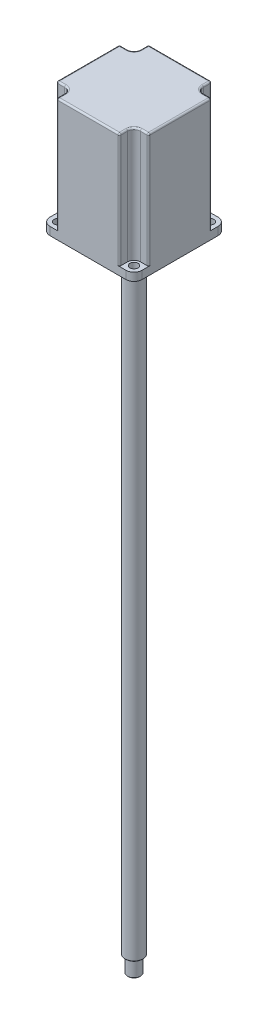
SolidWorks part; units mm, degrees
note: '?' marks a value the reader was unsure of.
material "1023 Carbon Steel Sheet (SS)"
ref_plane "Front" through (0, 0, 0) normal (0, 0, 1) x (1, 0, 0)
ref_plane "Top" through (0, 0, 0) normal (0, 1, 0) x (1, 0, 0)
ref_plane "Right" through (0, 0, 0) normal (1, 0, 0) x (0, 0, -1)
ref_axis "Axis1" through (-84.4107, 0, 0) along (1, 0, 0)?
ref_axis "Axis2" through (0, 64.3378, 0) along (0, -1, 0)?
ref_axis "Axis3" through (0, 0, -102.329) along (0, 0, 1)?
sketch "Sketch1" plane through (0, 0, 0) normal (0, 1, 0) x (1, 0, 0)
  line L1 (-28.5, -28.5) -> (28.5, -28.5)
  line L2 (-28.5, -28.5) -> (-28.5, 28.5)
  line L3 (-28.5, 28.5) -> (28.5, 28.5)
  line L4 (28.5, -28.5) -> (28.5, 28.5)
  line L5 (-28.5, -28.5) -> (28.5, 28.5) construction
  line L6 (-28.5, 28.5) -> (28.5, -28.5) construction
  point P0 (0, 0)
  dimension "D1" = 57
  dimension "D2" = 57
extrude "Extrude1" add sketch "Sketch1" along normal blind 76
hole_wizard "Ø5.0 (5) Diameter Hole1" positions "Sketch5" profile "Sketch4" hole size "Ø5.0" standard "ISO" end condition through all
sketch "Sketch5" plane through (0, 0, 0) normal (0, -1, 0) x (1, 0, 0)
  line L0 (-28.5, 28.5) -> (28.5, -28.5) construction
  line L3 (28.5, 28.5) -> (-28.5, -28.5) construction
  point P0 (-23.5, 23.5)
  point P1 (23.5, 23.5)
  point P3 (23.5, -23.5)
  point P5 (-23.5, -23.5)
  dimension "D1" = 47
  dimension "D2" = 47
sketch "Sketch4" plane through (-23.5, 0, 23.5) normal (1, 0, 0) x (0, 0, -1)
  line L0 (0, 0) -> (0, 76)
  line L1 (0, 76) -> (2.5, 76)
  line L2 (2.5, 76) -> (2.5, 0)
  line L5 (2.5, 0) -> (0, 0)
  line L11 (0, -6.35) -> (0, 107.95) construction
  dimension "Thru Hole Dia." = 5
  dimension "Thru Hole Depth" = 76
sketch "Sketch6" plane through (0, 76, 0) normal (0, 1, 0) x (1, 0, 0)
  line L0 (-19.5, 23.5) -> (-19.5, 32.5117)
  line L1 (-19.5, 32.5117) -> (-33.9089, 32.5117)
  line L2 (-33.9089, 32.5117) -> (-33.9089, 19.5)
  line L3 (-33.9089, 19.5) -> (-23.5, 19.5)
  line L4 (19.5, 23.5) -> (19.5, 36.4716)
  line L5 (19.5, 36.4716) -> (41.1684, 36.4716)
  line L6 (41.1684, 36.4716) -> (41.1684, 19.5)
  line L7 (41.1684, 19.5) -> (23.5, 19.5)
  line L8 (23.5, -19.5) -> (44.2522, -19.5)
  line L9 (44.2522, -19.5) -> (44.2522, -40.0504)
  line L10 (44.2522, -40.0504) -> (19.5, -40.0504)
  line L11 (19.5, -40.0504) -> (19.5, -23.5)
  line L12 (-23.5, -19.5) -> (-37.6708, -19.5)
  line L13 (-37.6708, -19.5) -> (-37.6708, -37.8282)
  line L14 (-37.6708, -37.8282) -> (-19.5, -37.8282)
  line L15 (-19.5, -37.8282) -> (-19.5, -23.5)
  circle A0 centre (-23.5, 23.5) radius 4
  circle A1 centre (23.5, 23.5) radius 4
  circle A2 centre (23.5, -23.5) radius 4
  circle A3 centre (-23.5, -23.5) radius 4
  circle M1 centre (-23.5, -23.5) radius 2.5
  circle M2 centre (23.5, -23.5) radius 2.5
  circle M3 centre (23.5, 23.5) radius 2.5
  circle M4 centre (-23.5, 23.5) radius 2.5
  line M5 (28.5, -28.5) -> (28.5, 28.5)
  line M6 (28.5, 28.5) -> (-28.5, 28.5)
  line M7 (-28.5, 28.5) -> (-28.5, -28.5)
  line M8 (-28.5, -28.5) -> (28.5, -28.5)
  dimension "D1" = 8
  dimension "D2" = 8
  dimension "D3" = 8
  dimension "D4" = 8
extrude "Extrude4" cut sketch "Sketch6" against normal blind 71 contours L2 L3 L0 L1 M7 M6 | A0 L0 L3 M6 M7 | A0 M4 | L7 L6 L5 L4 M6 M5 | A1 L7 L4 M5 M6 | A1 M3 | A2 M2 | A2 L11 L8 M8 M5 | L11 L10 L9 L8 M5 M8 | L14 L15 L12 L13 M8 M7 | A3 L12 L15 M7 M8 | A3 M1
fillet "Fillet1" radius 5 4 edges at (-28.5, 2.5, 28.5) (28.5, 2.5, 28.5) (28.5, 2.5, -28.5) (-28.5, 2.5, -28.5)
sketch "Sketch7" plane through (0, 76, 0) normal (0, 1, 0) x (1, 0, 0)
  circle A0 centre (0, 0) radius 3
  dimension "D1" = 6
extrude "Extrude5" add sketch "Sketch7" against normal blind 101 separate body
sketch "Sketch8" plane through (0, 0, 0) normal (0, -1, 0) x (1, 0, 0)
  circle A0 centre (0, 0) radius 19.05
  dimension "D1" = 38.1
extrude "Extrude6" add sketch "Sketch8" along normal blind 3
fillet "Fillet2" radius 1 24 edges at (-26, 76, 19.5) (-20.6716, 76, 20.6716) (-19.5, 76, 26) (0, 76, 28.5) (19.5, 76, 26) (20.6716, 76, 20.6716) (26, 76, 19.5) (28.5, 76, 0) (19.5, 76, -26) (26, 76, -19.5) (20.6716, 76, -20.6716) (-26, 76, -19.5) (-19.5, 76, -26) (-20.6716, 76, -20.6716) (0, 76, -28.5) (-28.5, 76, 0) (-19.5, 40.5, 28.5) (-28.5, 40.5, 19.5) (-28.5, 40.5, -19.5) (-19.5, 40.5, -28.5) (19.5, 40.5, -28.5) (28.5, 40.5, -19.5) (28.5, 40.5, 19.5) (19.5, 40.5, 28.5)
sketch "Sketch9" plane through (0, 0, 0) normal (0, -1, 0) x (1, 0, 0)
  circle A0 centre (0, 0) radius 5.5
  dimension "D1" = 11
extrude "Boss-Extrude1" add sketch "Sketch9" along normal blind 388
chamfer "Chamfer1" distance 0.5 angle 45 1 edges at (0, -388, -5.5)
sketch "Sketch10" plane through (0, -388, 0) normal (0, -1, 0) x (1, 0, 0)
  circle A0 centre (0, 0) radius 4
  dimension "D1" = 8
extrude "Boss-Extrude2" add sketch "Sketch10" along normal blind 10
chamfer "Chamfer2" distance 0.5 angle 45 1 edges at (0, -398, -4)
